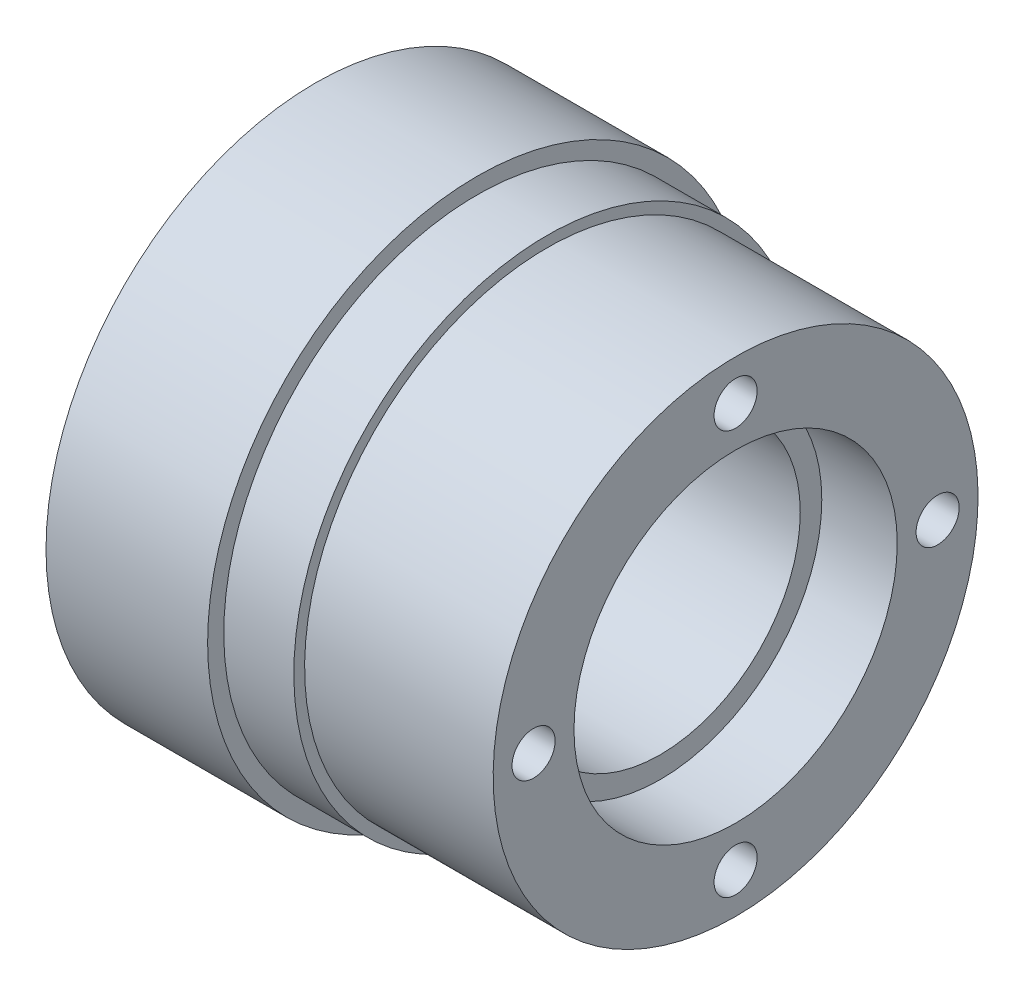
SolidWorks part; units mm, degrees
ref_plane "Front Plane" through (0, 0, 0) normal (0, 0, 1) x (1, 0, 0)
ref_plane "Top Plane" through (0, 0, 0) normal (0, 1, 0) x (1, 0, 0)
ref_plane "Right Plane" through (0, 0, 0) normal (1, 0, 0) x (0, 0, -1)
sketch "Sketch1" plane through (0, 0, 0) normal (0, 0, 1) x (1, 0, 0)
  line L0 (-19.5, 0) -> (19.5, 0) construction
  line L1 (-19.5, 13.5) -> (-15.3, 13.5)
  line L2 (-15.3, 13.5) -> (-15.3, 13)
  line L3 (-15.3, 13) -> (12.5, 13)
  line L4 (12.5, 13) -> (12.5, 15)
  line L5 (12.5, 15) -> (19.5, 15)
  line L6 (19.5, 15) -> (19.5, 22.5)
  line L7 (19.5, 22.5) -> (2, 22.5)
  line L8 (2, 22.5) -> (2, 23.5)
  line L9 (2, 23.5) -> (-4.5, 23.5)
  line L10 (-4.5, 23.5) -> (-4.5, 25)
  line L11 (-4.5, 25) -> (-19.5, 25)
  line L12 (-19.5, 25) -> (-19.5, 13.5)
  point P4 (0, 0)
  point P21 (2, 23)
  dimension "D1" = 39
  dimension "D2" = 7
  dimension "D3" = 26
  dimension "D4" = 27
  dimension "D5" = 30
  dimension "D6" = 4.2
  dimension "D7" = 50
  dimension "D8" = 45
  dimension "D9" = 47
  dimension "D10" = 15
  dimension "D11" = 17.5
revolve "Revolve1" add sketch "Sketch1" angle 360 about L0
sketch "Sketch2" plane through (19.5, 0, 0) normal (1, 0, 0) x (0, 0, -1)
  line L0 (0, 22.5) -> (0, 15) construction
  circle A0 centre (0, 18.75) radius 2
  circle A1 centre (0, 0) radius 22.5 construction
  circle A2 centre (0, 0) radius 22.5 construction
  circle A3 centre (0, 0) radius 15 construction
  circle A4 centre (18.75, 0) radius 2
  circle A5 centre (0, -18.75) radius 2
  circle A6 centre (-18.75, 0) radius 2
  point P21 (0, 0)
  dimension "D1" = 4
  dimension "D2" = 18.75
  dimension "D3" = 18.75
extrude "Cut-Extrude1" cut sketch "Sketch2" against normal blind 10
sketch "Sketch3" plane through (-19.5, 0, 0) normal (-1, 0, 0) x (0, 0, 1)
  line L0 (0, 13.5) -> (0, 25) construction
  circle A0 centre (0, 0) radius 13.5 construction
  circle A1 centre (0, 0) radius 13.5 construction
  circle A2 centre (0, 0) radius 25 construction
  circle A3 centre (0, 19.25) radius 2
  circle A4 centre (19.25, 0) radius 2
  circle A5 centre (0, -19.25) radius 2
  circle A6 centre (-19.25, 0) radius 2
  point P19 (0, 0)
  dimension "D1" = 4
  dimension "D2" = 19.25
  dimension "D3" = 19.25
extrude "Cut-Extrude2" cut sketch "Sketch3" against normal blind 10
equation "\"mini-flipper-shaft-diameter\"= 26mm"
equation "\"mini-shaft-ring-groove-diam\"= 7.8mm"
equation "\"mini-shaft-ring-groove-width\"= 1mm"
equation "\"dtCoverPlate-DistFrom-GearCent\" = 73mm"
equation "\"wormGearShaft-L\" = \"dtCoverPlate-DistFrom-GearCent\" - 27.75 + 3.75"
equation "\"wormGearShaft-Dsmall\" = 6mm"
equation "\"wormGearShaft-Dworm\" = 12mm"
equation "\"wormL-D\" = 12mm"
equation "\"wormR-D\" = 15mm"
equation "\"wormGearL-D\" = 40mm"
equation "\"wormGearR-D\" = 50mm"
equation "\"D7@Sketch1\"=\"wormGearR-D\""
